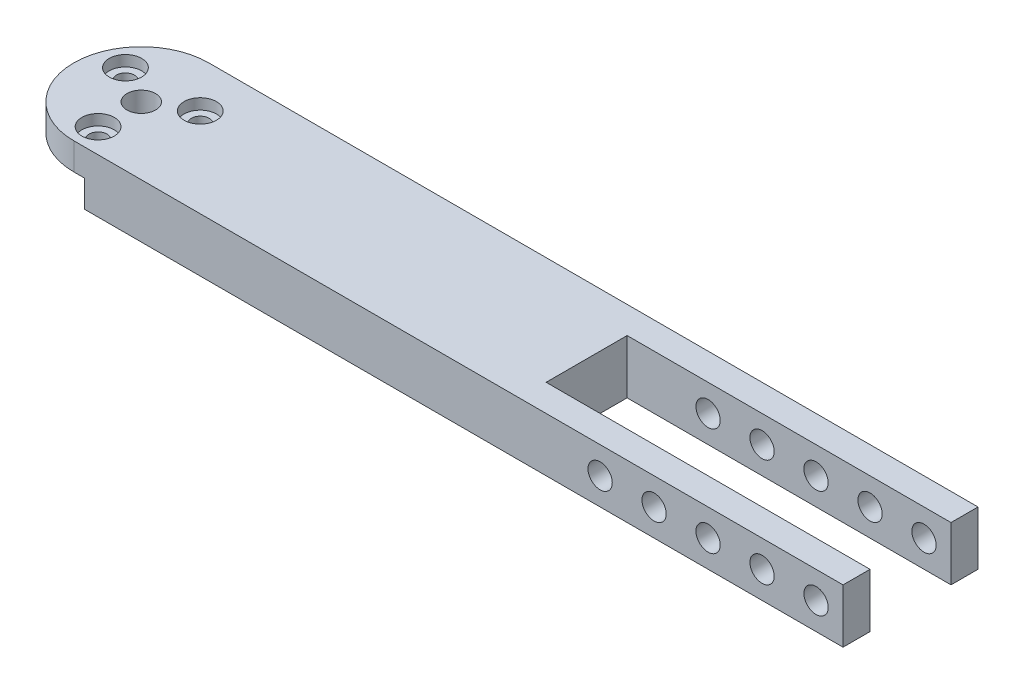
SolidWorks part; units mm, degrees
ref_plane "Front Plane" through (0, 0, 0) normal (0, 0, 1) x (1, 0, 0)
ref_plane "Top Plane" through (0, 0, 0) normal (0, 1, 0) x (1, 0, 0)
ref_plane "Right Plane" through (0, 0, 0) normal (1, 0, 0) x (0, 0, -1)
sketch "Sketch1" plane through (0, 0, 0) normal (0, 1, 0) x (1, 0, 0)
  line L1 (0, 0) -> (250, 0)
  line L2 (0, 0) -> (0, 25)
  line L3 (0, 25) -> (250, 25)
  line L4 (250, 0) -> (250, 25)
  dimension "D1" = 25
  dimension "D2" = 250
extrude "Boss-Extrude1" add sketch "Sketch1" along normal blind 10
sketch "Sketch2" plane through (0, 10, 0) normal (0, 1, 0) x (1, 0, 0)
  line L0 (0, 12.5) -> (250, 12.5) construction
  line L1 (0, 25) -> (0, 0) construction
  line L2 (250, 0) -> (250, 25) construction
  circle A0 centre (12.5, 12.5) radius 2.65
  dimension "D1" = 12.5
  dimension "D2" = 5.3
extrude "Cut-Extrude1" cut sketch "Sketch2" against normal up to next contours A0 | A0 region at (12.5, 10, -12.5)
fillet "Fillet1" radius 12.5 2 edges at (0, 5, 0) (0, 5, -25)
sketch "Sketch3" plane through (0, 0, -25) normal (0, 0, -1) x (-1, 0, 0)
  line L0 (-12.5, 5) -> (-250, 5) construction
  line L1 (-12.5, 0) -> (-12.5, 10) construction
  line L2 (-250, 10) -> (-250, 0) construction
  circle A0 centre (-244.5, 5) radius 2.25
  circle A1 centre (-230.5, 5) radius 2.25
  dimension "D1" = 4.5
  dimension "D2" = 5.5
  dimension "D4" = 14
  dimension "D3" = 2
extrude "Cut-Extrude2" cut sketch "Sketch3" against normal through all
sketch "Sketch5" plane through (0, 10, 0) normal (0, 1, 0) x (1, 0, 0)
  line L0 (244.5, 25) -> (244.5, 0) construction
  line L1 (250, 25) -> (12.5, 25) construction
  line L2 (12.5, 0) -> (250, 0) construction
  line L3 (250, 0) -> (250, 25) construction
  line L4 (244.5, 12.5) -> (250, 12.5) construction
  line L5 (240.85, 17) -> (248.15, 17)
  line L6 (240.85, 17) -> (240.85, 21)
  line L7 (240.85, 21) -> (248.15, 21)
  line L8 (248.15, 17) -> (248.15, 21)
  line L9 (240.85, 17) -> (248.15, 21) construction
  line L10 (240.85, 21) -> (248.15, 17) construction
  line L11 (240.85, 4) -> (248.15, 4)
  line L12 (248.15, 8) -> (248.15, 4)
  line L13 (240.85, 8) -> (248.15, 8)
  line L14 (240.85, 8) -> (240.85, 4)
  line L15 (226.85, 17) -> (226.85, 21)
  line L16 (226.85, 17) -> (234.15, 17)
  line L17 (234.15, 17) -> (234.15, 21)
  line L18 (226.85, 21) -> (234.15, 21)
  line L19 (226.85, 4) -> (234.15, 4)
  line L20 (234.15, 8) -> (234.15, 4)
  line L21 (226.85, 8) -> (234.15, 8)
  line L22 (226.85, 8) -> (226.85, 4)
  point P8 (244.5, 19)
  dimension "D1" = 5.5
  dimension "D2" = 7.3
  dimension "D3" = 4
  dimension "D4" = 6
  dimension "D6" = 14
  dimension "D5" = 2
extrude "Cut-Extrude5" cut sketch "Sketch5" against normal up to next
sketch "Sketch6" plane through (0, 0, 0) normal (0, -1, 0) x (1, 0, 0)
  circle A0 centre (12.5, -12.5) radius 12.65
  dimension "D1" = 25.3
extrude "Cut-Extrude6" cut sketch "Sketch6" against normal blind 5
sketch "Sketch7" plane through (0, 5, 0) normal (0, -1, 0) x (1, 0, 0)
  line L0 (12.5, -12.5) -> (12.5, 0.15) construction
  circle A0 centre (12.5, -12.5) radius 12.65 construction
  circle A1 centre (12.5, -4.5) radius 1.65
  circle A5 centre (19.4282, -16.5) radius 1.65
  circle A6 centre (5.5718, -16.5) radius 1.65
  point P15 (12.5, -12.5)
  point P17 (12.5, -12.5)
  dimension "D1" = 3.3
  dimension "D2" = 8
  dimension "D4" = 6.9282
  dimension "D5" = 4
  dimension "D3" = 3
extrude "Cut-Extrude7" cut sketch "Sketch7" against normal up to next
sketch "Sketch9" plane through (0, 10, 0) normal (0, 1, 0) x (1, 0, 0)
  line L0 (12.5, 4.5) -> (12.5, 12.5) construction
  circle A4 centre (5.5718, 16.5) radius 3
  circle A7 centre (12.5, 4.5) radius 3
  circle A8 centre (19.4282, 16.5) radius 3
  point P10 (12.5, 12.5)
  dimension "D1" = 6
  dimension "D2" = 3
  dimension "D3" = 6.9282
  dimension "D4" = 4
extrude "Cut-Extrude9" cut sketch "Sketch9" against normal blind 2
sketch "Sketch10" plane through (0, 10, 0) normal (0, 1, 0) x (1, 0, 0)
  line L5 (0, 12.5) -> (250, 12.5) construction
  line L6 (250, 0) -> (250, 25) construction
  line L7 (250, 25) -> (12.5, 25) construction
  line L8 (95, 5) -> (155, 5)
  line L9 (95, 5) -> (95, 20)
  line L10 (95, 20) -> (155, 20)
  line L12 (95, 5) -> (155, 20) construction
  line L13 (95, 20) -> (155, 5) construction
  line L14 (155, 5) -> (155, 0) construction
  line L15 (12.5, 0) -> (250, 0) construction
  line L16 (155, 20) -> (155, 25)
  line L17 (155, 0) -> (250, 0)
  line L18 (155, 0) -> (155, 5)
  line L19 (155, 25) -> (250, 25)
  line L20 (250, 0) -> (250, 25)
  point P5 (125, 12.5)
  dimension "D1" = 60
  dimension "D2" = 5
extrude "Cut-Extrude10" cut sketch "Sketch10" against normal through all
sketch "Sketch11" plane through (0, 0, 0) normal (0, 0, 1) x (1, 0, 0)
  line L0 (155, 5) -> (12.5, 5) construction
  line L1 (155, 0) -> (155, 10) construction
  circle A0 centre (150, 5) radius 2.25
  circle A1 centre (140, 5) radius 2.25
  circle A2 centre (130, 5) radius 2.25
  circle A3 centre (120, 5) radius 2.25
  circle A4 centre (110, 5) radius 2.25
  dimension "D1" = 4.5
  dimension "D2" = 5
  dimension "D4" = 10
  dimension "D3" = 5
extrude "Cut-Extrude11" cut sketch "Sketch11" against normal through all
